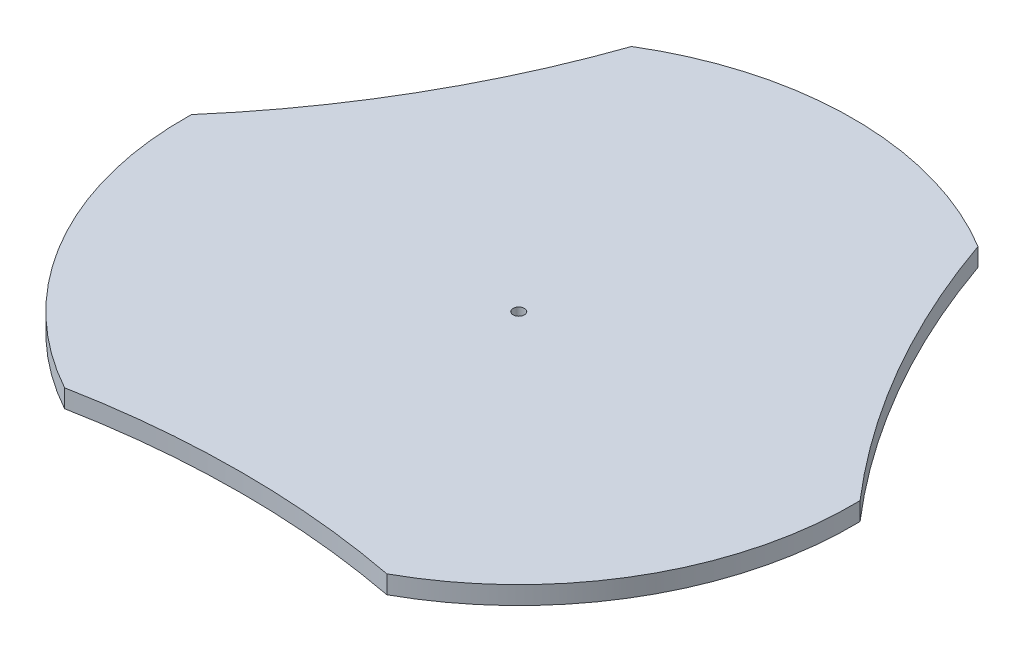
SolidWorks part; units mm, degrees
ref_plane "Front Plane" through (0, 0, 0) normal (0, 0, 1) x (1, 0, 0)
ref_plane "Top Plane" through (0, 0, 0) normal (0, 1, 0) x (1, 0, 0)
ref_plane "Right Plane" through (0, 0, 0) normal (1, 0, 0) x (0, 0, -1)
sketch "Sketch1" plane through (0, 0, 0) normal (0, 1, 0) x (1, 0, 0)
  circle A0 centre (0, 0) radius 37
  dimension "D1" = 74
extrude "Boss-Extrude1" add sketch "Sketch1" along normal blind 1.6
sketch "Sketch3" plane through (0, 1.6, 0) normal (0, 1, 0) x (1, 0, 0)
  line L0 (0, 0) -> (-17101.0072, 46984.631) construction
  line L1 (0, 0) -> (17101.0072, 46984.631) construction
  line L2 (0, 0) -> (0, 50000) construction
  line L3 (-12.6547, 34.7686) -> (-9.9186, 27.2511) construction
  line L4 (12.6547, 34.7686) -> (9.9186, 27.2511) construction
  line L5 (23.7831, -28.3436) -> (18.6408, -22.2153) construction
  line L6 (36.4379, -6.425) -> (28.5594, -5.0358) construction
  line L7 (-36.4379, -6.425) -> (-28.5594, -5.0358) construction
  line L8 (-23.7831, -28.3436) -> (-18.6408, -22.2153) construction
  line L9 (2.789, 31.8782) -> (0, 0) construction
  arc A0 (-12.6547, 34.7686) -> (12.6547, 34.7686) centre (0, 0) cw construction
  circle A1 centre (0, 0) radius 37 construction
  arc A2 (-9.9186, 27.2511) -> (9.9186, 27.2511) centre (0, 0) cw construction
  circle A3 centre (2.789, 31.8782) radius 1.75
  arc A4 (28.5594, -5.0358) -> (18.6408, -22.2153) centre (0, 0) cw construction
  arc A5 (36.4379, -6.425) -> (23.7831, -28.3436) centre (0, 0) cw construction
  circle A6 centre (26.2129, -18.3544) radius 1.75
  arc A7 (-18.6408, -22.2153) -> (-28.5594, -5.0358) centre (0, 0) cw construction
  arc A8 (-23.7831, -28.3436) -> (-36.4379, -6.425) centre (0, 0) cw construction
  circle A9 centre (-29.0018, -13.5238) radius 1.75
  point P33 (0, 0)
  dimension "D5" = 3.5
  dimension "D1" = 20
  dimension "D2" = 20
  dimension "D3" = 8
  dimension "D6" = 32
  dimension "D7" = 5
  dimension "D4" = 3
sketch "Sketch5" plane through (0, 1.6, 0) normal (0, 1, 0) x (1, 0, 0)
  circle A0 centre (86.6025, 50) radius 75.5001
  dimension "D1" = 100
extrude "Cut-Extrude2" cut sketch "Sketch5" against normal through all
sketch "Sketch7" plane through (0, 1.6, 0) normal (0, 1, 0) x (1, 0, 0)
  circle A0 centre (0, 0) radius 0.5
  dimension "D1" = 1
extrude "Cut-Extrude3" cut sketch "Sketch7" against normal through all
extrude "Cut-Extrude4" cut sketch "Sketch3" against normal through all
sketch "Sketch8" plane through (0, 1.6, 0) normal (0, 1, 0) x (1, 0, 0)
  line L0 (-14.2641, 35.0556) -> (47112.9297, 8344.8514) construction
  line L1 (-6.5986, 37.4227) -> (-11.9778, 36.4742) construction
  line L2 (-5.904, 33.4835) -> (0, 0) construction
  line L3 (0, -1000) -> (0, 49000) construction
  circle A0 centre (-5.904, 33.4835) radius 4 construction
  arc A1 (12.6547, 34.7686) -> (36.4379, -6.425) centre (0, 0) ccw construction
  circle A2 centre (-5.904, 33.4835) radius 1.65
  dimension "D1" = 8
  dimension "D3" = 3.3
  dimension "D2" = 1
  dimension "D4" = 10
extrude "Cut-Extrude5" cut sketch "Sketch8" against normal through all
pattern_circular "CirPattern2" count 3 over 360 about axis through (0, 1.6, 0) along (0, -1, 0) of "Cut-Extrude2", "Cut-Extrude5" reverse direction yes
sketch "Sketch9" plane through (0, 1.6, 0) normal (0, 1, 0) x (1, 0, 0)
  line L1 (-36.4379, -28.3436) -> (36.4379, -28.3436)
  line L2 (-36.4379, -28.3436) -> (-36.4379, 37)
  line L3 (-36.4379, 37) -> (36.4379, 37)
  line L4 (36.4379, -28.3436) -> (36.4379, 37)
  arc A0 (12.6547, 34.7686) -> (-12.6547, 34.7686) centre (0, 0) ccw construction
  dimension "D1" = 72.8758
  dimension "D2" = 65.3436
sketch "Sketch10" plane through (0, 1.6, 0) normal (0, 1, 0) x (1, 0, 0)
  circle A0 centre (0, 0) radius 29.5
  dimension "D1" = 59
extrude "Cut-Extrude7" cut sketch "Sketch10" against normal blind 10 flip side to cut
sketch "Sketch11" plane through (0, 1.6, 0) normal (0, 1, 0) x (1, 0, 0)
  line L0 (-29.4936, -988.4588) -> (-29.4936, 49011.5412) construction
  line L1 (29.4936, -998.5133) -> (29.4936, 49001.4867) construction
  line L2 (-1012.334, 29.5) -> (48987.666, 29.5) construction
  line L3 (-1020.8898, -25.8499) -> (48979.1102, -25.8499) construction
  line L5 (-29.4936, 29.5) -> (29.4936, 29.5)
  line L6 (-29.4936, 29.5) -> (-29.4936, -25.8499)
  line L7 (-29.4936, -25.8499) -> (29.4936, -25.8499)
  line L8 (29.4936, 29.5) -> (29.4936, -25.8499)
  arc A0 (15.2798, 25.2345) -> (-15.2798, 25.2345) centre (0, 0) ccw construction
  dimension "D1" = 58.9872
  dimension "D2" = 55.3499
